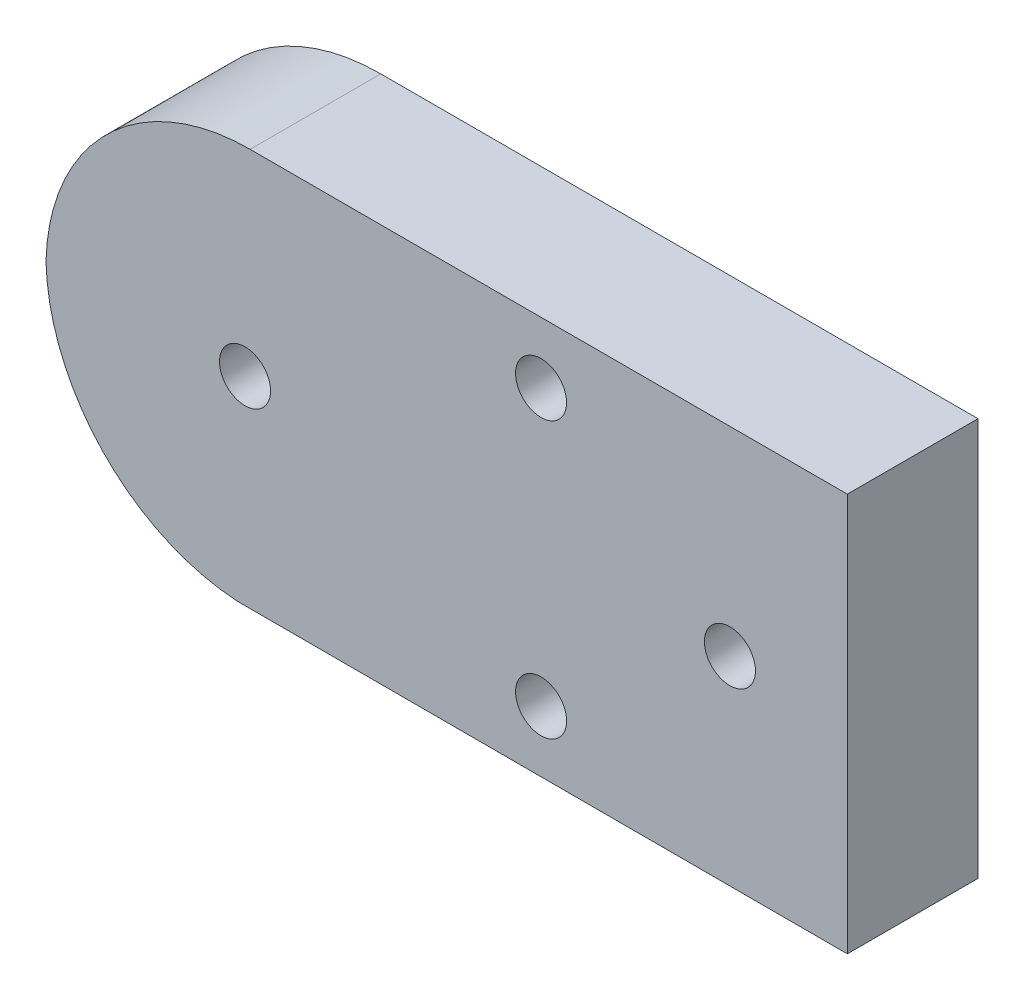
SolidWorks part; units mm, degrees
ref_plane "Front Plane" through (0, 0, 0) normal (0, 0, 1) x (1, 0, 0)
ref_plane "Top Plane" through (0, 0, 0) normal (0, 1, 0) x (1, 0, 0)
ref_plane "Right Plane" through (0, 0, 0) normal (1, 0, 0) x (0, 0, -1)
sketch "Sketch1" plane through (0, 0, 0) normal (0, 0, 1) x (1, 0, 0)
  line L0 (0, 0) -> (23.75, 0)
  line L1 (23.75, 3.75) -> (6.7823, 3.75)
  line L2 (23.75, -3.75) -> (6.7823, -3.75)
  line L3 (0, 0) -> (-9.75, 0)
  line L4 (-9.75, -9.75) -> (-9.75, 9.75)
  line L5 (-9.75, 9.75) -> (29.5, 9.75)
  line L6 (29.5, 9.75) -> (29.5, -9.75)
  line L7 (-9.75, -9.75) -> (29.5, -9.75)
  line L8 (29.5, 9.75) -> (29.5, 6.75)
  line L9 (29.5, 6.75) -> (14.5, 6.75)
  line L10 (29.5, -9.75) -> (29.5, -6.75)
  line L11 (29.5, -6.75) -> (14.5, -6.75)
  circle A0 centre (0, 0) radius 7.75
  circle A1 centre (23.75, 0) radius 3.75
  arc A2 (4.901, 6.0035) -> (11.225, 3.75) centre (11.225, 13.75) ccw
  arc A3 (11.225, -3.75) -> (4.901, -6.0035) centre (11.225, -13.75) ccw
  circle A4 centre (14.5, 6.75) radius 1.25
  circle A6 centre (14.5, -6.75) radius 1.25
  point P21 (29.5, 0)
  dimension "D1" = 15.5
  dimension "D3" = 7.5
  dimension "D4" = 9.75
  dimension "D8" = 10
  dimension "D9" = 10
  dimension "D7" = 2.5
  dimension "D11" = 15
  dimension "D10" = 2.5
  dimension "D2" = 23.75
  dimension "D5" = 9.75
  dimension "D6" = 39.25
  dimension "D12" = 15
extrude "Boss-Extrude4" add sketch "Sketch1" along normal blind 4 contours A6 L6 A4 L5 L4 A0 A2 L1 A1 L2 A3 L7 region at (-9.3117, 4.875, 0)
fillet "Fillet1" radius 10 2 edges at (-9.75, -9.75, 2) (-9.75, 9.75, 2)
sketch "Sketch2" plane through (0, 0, 4) normal (0, 0, 1) x (1, 0, 0)
  line L0 (0, 9.7532) -> (29.5, 9.75)
  line L1 (29.5, 9.75) -> (29.5, -9.75)
  line L2 (29.5, -9.75) -> (-0.681, -9.7294)
  circle A0 centre (0, 0) radius 1.25
  circle A1 centre (23.75, 0) radius 1.25
  circle A2 centre (0, 0) radius 9.7532
  circle M1 centre (14.5, -6.75) radius 1.25
  circle M2 centre (14.5, 6.75) radius 1.25
  arc M3 (0.25, 9.75) -> (-9.7469, 0) centre (0.25, -0.25) ccw
  arc M4 (-9.7469, 0) -> (0.25, -9.75) centre (0.25, 0.25) ccw
  line M6 (29.5, -9.75) -> (29.5, 9.75)
  line M7 (29.5, 9.75) -> (0.25, 9.75)
  arc M8 (11.225, -3.75) -> (4.901, -6.0035) centre (11.225, -13.75) ccw
  arc M9 (4.901, -6.0035) -> (4.901, 6.0035) centre (0, 0) cw
  arc M10 (4.901, 6.0035) -> (11.225, 3.75) centre (11.225, 13.75) ccw
  line M11 (11.225, 3.75) -> (23.75, 3.75)
  arc M12 (23.75, 3.75) -> (23.75, -3.75) centre (23.75, 0) cw
  line M13 (23.75, -3.75) -> (11.225, -3.75)
extrude "Boss-Extrude5" add sketch "Sketch2" along normal blind 1.2 contours A2 L2 M10 M3 M4 M8 M9 | A2 A0 M8 M10 M9 | A2 L2 M10 M11 M12 M13 M8 M6 M7 M2 M1 | A2 A1 M8 M13 M12 M11 M10 region at (29.1485, 0, 4) region at (5.2395, 7.9049, 4) region at (17.8705, 0, 4) region at (9.3045, 2.0112, 4)
sketch "Sketch3" plane through (0, 0, 5.2) normal (0, 0, 1) x (1, 0, 0)
  line L0 (0, 9.75) -> (29.5, 9.75)
  line L1 (29.5, 9.75) -> (29.5, -9.75)
  line L2 (29.5, -9.75) -> (0, -9.75)
  circle A0 centre (0, 0) radius 1.25
  circle A1 centre (23.75, 0) radius 1.25
  circle A2 centre (0, 0) radius 9.75
  line M2 (29.5, 9.75) -> (0.25, 9.75)
  arc M3 (0.25, 9.75) -> (-9.7469, 0) centre (0.25, -0.25) ccw
  arc M4 (-9.7469, 0) -> (-0.3884, -9.7296) centre (0.25, 0.25) ccw
  line M5 (-0.3884, -9.7296) -> (29.5, -9.75)
  line M6 (29.5, -9.75) -> (29.5, 9.75)
  circle M8 centre (14.5, 6.75) radius 1.25
  circle M9 centre (14.5, -6.75) radius 1.25
extrude "Boss-Extrude6" add sketch "Sketch3" along normal blind 1.2 contours A2 A0 M5 M3 M4 | A2 A1 M5 M6 M2 M3 M9 M8 region at (18.5081, 0.0068, 5.2) region at (6.7419, 6.6566, 5.2)
